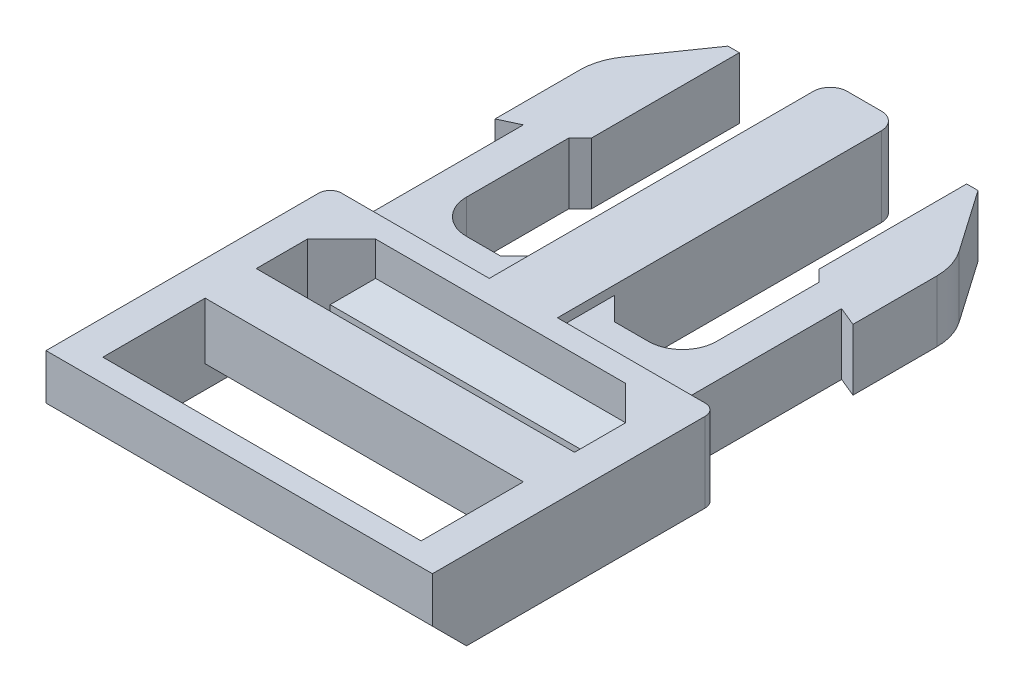
SolidWorks part; units mm, degrees
ref_plane "Front Plane" through (0, 0, 0) normal (0, 0, 1) x (1, 0, 0)
ref_plane "Top Plane" through (0, 0, 0) normal (0, 1, 0) x (1, 0, 0)
ref_plane "Right Plane" through (0, 0, 0) normal (1, 0, 0) x (0, 0, -1)
sketch "Sketch1" plane through (0, 0, 0) normal (0, 1, 0) x (1, 0, 0)
  line L1 (-14, 1.5) -> (14, 1.5)
  line L2 (-14, 1.5) -> (-14, -1.5)
  line L3 (-14, -1.5) -> (14, -1.5)
  line L4 (14, 1.5) -> (14, -1.5)
  line L5 (-14, 1.5) -> (14, -1.5) construction
  line L6 (-14, -1.5) -> (14, 1.5) construction
  point P0 (0, 0)
  dimension "D1" = 3
  dimension "D2" = 28
extrude "Boss-Extrude1" add sketch "Sketch1" along normal blind 7
sketch "Sketch2" plane through (0, 0, -1.5) normal (0, 0, -1) x (-1, 0, 0)
  line L0 (-14, 7) -> (14, 7) construction
  line L1 (14, 0) -> (11, 0)
  line L2 (14, 0) -> (14, 7)
  line L3 (14, 7) -> (11, 7)
  line L4 (11, 0) -> (11, 7)
  line L6 (-14, 0) -> (-11, 0)
  line L7 (-14, 0) -> (-14, 7)
  line L8 (-14, 7) -> (-11, 7)
  line L9 (-11, 0) -> (-11, 7)
  dimension "D1" = 3
  dimension "D2" = 3
extrude "Boss-Extrude2" add sketch "Sketch2" along normal blind 26
sketch "Sketch3" plane through (0, 0, -1.5) normal (0, 0, -1) x (-1, 0, 0)
  line L0 (-11, 7) -> (11, 7) construction
  line L1 (-3, 7) -> (3, 7)
  line L2 (-3, 7) -> (-3, 0)
  line L3 (-3, 0) -> (3, 0)
  line L4 (3, 7) -> (3, 0)
  line L5 (-11, 0) -> (11, 0) construction
  line L7 (-11, 0) -> (-11, 7) construction
  dimension "D1" = 6
  dimension "D2" = 8
extrude "Boss-Extrude3" add sketch "Sketch3" along normal blind 27
sketch "Sketch4" plane through (0, 7, 0) normal (0, 1, 0) x (1, 0, 0)
  line L0 (-14, 12.5) -> (-15.7, 11.7073)
  line L1 (-14, 27.5) -> (-14, -1.5) construction
  line L2 (-15.7, 11.7073) -> (-15.7, 16.7073)
  line L3 (-15.7, 16.7073) -> (-14, 19.5)
  line L4 (-14, 19.5) -> (-14, 12.5)
  line L5 (-3, 1.5) -> (-11, 1.5) construction
  line L6 (14, 12.5) -> (15.7, 11.8005)
  line L7 (14, -1.5) -> (14, 27.5) construction
  line L8 (15.7, 11.8005) -> (15.7, 16.8005)
  line L9 (15.7, 16.8005) -> (14, 19.5)
  line L10 (14, 19.5) -> (14, 12.5)
  dimension "D1" = 11
  dimension "D2" = 65
  dimension "D3" = 1.7
  dimension "D4" = 18
  dimension "D5" = 5
  dimension "D6" = 1.7
  dimension "D7" = 5
extrude "Boss-Extrude4" add sketch "Sketch4" against normal blind 7
chamfer "Chamfer1" distance 2 angle 45 2 edges at (3, 3.5, -1.5) (-3, 3.5, -1.5)
fillet "Fillet1" radius 3 2 edges at (11, 3.5, -1.5) (-11, 3.5, -1.5)
sketch "Sketch5" plane through (0, 7, 0) normal (0, 1, 0) x (1, 0, 0)
  line L0 (-14, 21.5) -> (-11, 27.5)
  line L1 (-14, 27.5) -> (-14, 19.5) construction
  line L2 (-11, 27.5) -> (-14, 27.5)
  line L3 (-14, 27.5) -> (-14, 21.5)
  line L4 (-5, 1.5) -> (-8, 1.5) construction
  line L5 (14, 21.5) -> (11, 27.5)
  line L6 (14, 19.5) -> (14, 27.5) construction
  line L7 (11, 27.5) -> (14, 27.5)
  line L9 (14, 27.5) -> (14, 21.5)
  dimension "D1" = 20
extrude "Cut-Extrude1" cut sketch "Sketch5" against normal blind 8
sketch "Sketch6" plane through (0, 0, 1.5) normal (0, 0, 1) x (1, 0, 0)
  line L0 (-14, 7) -> (-14, 0) construction
  line L1 (-17, 7) -> (17, 7)
  line L2 (-17, 7) -> (-17, 0)
  line L3 (-17, 0) -> (17, 0)
  line L4 (17, 7) -> (17, 0)
  line L5 (14, 7) -> (14, 0) construction
  line L6 (-14, 7) -> (14, 7) construction
  dimension "D1" = 3
  dimension "D2" = 3
  dimension "D3" = 0
extrude "Boss-Extrude5" add sketch "Sketch6" along normal blind 25
sketch "Sketch8" plane through (0, 7, 0) normal (0, 1, 0) x (1, 0, 0)
  line L0 (-17, -26.5) -> (-17, -1.5) construction
  line L1 (-14, -3.5) -> (14, -3.5)
  line L2 (-14, -3.5) -> (-14, -24.5)
  line L3 (-14, -24.5) -> (14, -24.5)
  line L4 (14, -3.5) -> (14, -24.5)
  line L5 (17, -26.5) -> (17, -1.5) construction
  line L6 (-14, -1.5) -> (-17, -1.5) construction
  line L7 (17, -26.5) -> (-17, -26.5) construction
  dimension "D1" = 3
  dimension "D2" = 3
  dimension "D3" = 2
  dimension "D4" = 2
extrude "Cut-Extrude2" cut sketch "Sketch8" against normal blind 25
chamfer "Chamfer2" distance 3 angle 45 2 edges at (14, 3.5, 3.5) (-14, 3.5, 3.5)
fillet "Fillet2" radius 1 2 edges at (17, 3.5, 1.5) (-17, 3.5, 1.5)
sketch "Sketch9" plane through (0, 7, 0) normal (0, 1, 0) x (1, 0, 0)
  line L0 (-14, -6.5) -> (-14, -24.5) construction
  line L1 (-14, -11.5) -> (14, -11.5)
  line L2 (-14, -11.5) -> (-14, -15.5)
  line L3 (-14, -15.5) -> (14, -15.5)
  line L4 (14, -11.5) -> (14, -15.5)
  line L5 (14, -24.5) -> (14, -6.5) construction
  line L6 (11, -3.5) -> (-11, -3.5) construction
  dimension "D1" = 8
extrude "Boss-Extrude6" add sketch "Sketch9" against normal blind 7
sketch "Sketch10" plane through (0, 0, 24.5) normal (0, 0, -1) x (-1, 0, 0)
  line L0 (14, 0) -> (14, 7) construction
  line L1 (-14, 0) -> (14, 0)
  line L2 (-14, 0) -> (-14, 2)
  line L3 (-14, 2) -> (14, 2)
  line L4 (14, 0) -> (14, 2)
  dimension "D1" = 2
extrude "Boss-Extrude7" add sketch "Sketch10" along normal blind 4
chamfer "Chamfer3" distance 1 angle 45 1 edges at (0, 2, 20.5)
chamfer "Chamfer4" distance 3 angle 45 1 edges at (0, 2, 24.5)
chamfer "Chamfer5" distance 2 angle 45 1 edges at (0, 0, 15.5)
fillet "Fillet4" radius 1.5 2 edges at (3, 3.5, -28.5) (-3, 3.5, -28.5)
sketch "Sketch11" plane through (-11, 0, 0) normal (1, 0, 0) x (0, 0, -1)
  line L0 (27.5, 0) -> (4.5, 0) construction
  line L1 (27.5, 7) -> (13.5, 7)
  line L2 (27.5, 7) -> (27.5, 0)
  line L3 (27.5, 0) -> (13.5, 0)
  line L4 (13.5, 7) -> (13.5, 0)
  dimension "D1" = 14
extrude "Boss-Extrude8" add sketch "Sketch11" along normal blind 1
chamfer "Chamfer6" distance 1 angle 45 1 edges at (-10, 3.5, -13.5)
sketch "Sketch12" plane through (11, 0, 0) normal (-1, 0, 0) x (0, 0, 1)
  line L0 (-27.5, 7) -> (-4.5, 7) construction
  line L1 (-27.5, 0) -> (-13.5, 0)
  line L2 (-27.5, 0) -> (-27.5, 7)
  line L3 (-27.5, 7) -> (-13.5, 7)
  line L4 (-13.5, 0) -> (-13.5, 7)
  dimension "D1" = 14
extrude "Boss-Extrude9" add sketch "Sketch12" along normal blind 1
chamfer "Chamfer7" distance 1 angle 45 1 edges at (10, 3.5, -13.5)
sketch "Sketch13" plane through (15.7, 0, 0) normal (1, 0, 0) x (0, 0, -1)
  line L0 (-1.5, 7) -> (-1.5, 0) construction
  line L1 (-1.5, 6.2) -> (28.5, 6.2)
  line L2 (28.5, 0.8) -> (28.5, 0)
  line L3 (-1.5, 0.8) -> (28.5, 0.8)
  line L5 (28.5, 7) -> (28.5, 0) construction
  line L6 (-1.5, 0.8) -> (-1.5, 0)
  line L7 (-1.5, 7) -> (28.5, 7)
  line L8 (-1.5, 7) -> (-1.5, 6.2)
  line L9 (-1.5, 0) -> (28.5, 0)
  line L10 (28.5, 7) -> (28.5, 6.2)
  dimension "D1" = 0.8
  dimension "D2" = 0.8
extrude "Cut-Extrude3" cut sketch "Sketch13" against normal blind 12.7
sketch "Sketch14" plane through (-15.7, 0, 0) normal (-1, 0, 0) x (0, 0, 1)
  line L0 (-28.5, 0) -> (-28.5, 7) construction
  line L1 (-28.5, 6.2) -> (1.5, 6.2)
  line L2 (1.5, 0.8) -> (1.5, 0)
  line L3 (-28.5, 0.8) -> (1.5, 0.8)
  line L5 (1.5, 7) -> (1.5, 0) construction
  line L6 (-28.5, 0.8) -> (-28.5, 0)
  line L7 (1.5, 7) -> (-28.5, 7)
  line L8 (1.5, 7) -> (1.5, 6.2)
  line L9 (1.5, 0) -> (-28.5, 0)
  line L10 (-28.5, 7) -> (-28.5, 6.2)
  dimension "D1" = 0.8
  dimension "D2" = 0.8
extrude "Cut-Extrude4" cut sketch "Sketch14" against normal blind 12.7
sketch "Sketch15" plane through (0, 6.2, 0) normal (0, 1, 0) x (1, 0, 0)
  line L0 (-15.7, 16.7073) -> (-15.7, 20.7469)
  line L1 (-15.7, 20.7469) -> (-11, 27.5)
  line L2 (-11, 27.5) -> (-14, 19.5)
  line L3 (-14, 19.5) -> (-15.7, 16.7073)
  line L4 (15.7, 16.8005) -> (15.7, 20.7469)
  line L5 (15.7, 20.7469) -> (11, 27.5)
  line L6 (11, 27.5) -> (14, 19.5)
  line L7 (14, 19.5) -> (15.7, 16.8005)
extrude "Boss-Extrude10" add sketch "Sketch15" against normal blind 5.4
fillet "Fillet5" radius 5 2 edges at (-15.7, 3.5, -20.7469) (15.7, 3.5, -20.7469)
chamfer "Chamfer8" distance 3 angle 45 1 edges at (0, 0, 26.5)
sketch "Sketch16" plane through (0, 0, 11.5) normal (0, 0, -1) x (-1, 0, 0)
  line L0 (14, 0) -> (14, 7) construction
  line L1 (-14, 7) -> (14, 7)
  line L2 (-14, 7) -> (-14, 5)
  line L3 (-14, 5) -> (14, 5)
  line L4 (14, 7) -> (14, 5)
  dimension "D1" = 2
extrude "Boss-Extrude11" add sketch "Sketch16" along normal blind 2
chamfer "Chamfer9" distance 2 angle 45 1 edges at (0, 5, 11.5)
sketch "Sketch17" plane through (0, 0, 3.5) normal (0, 0, 1) x (1, 0, 0)
  line L1 (15.6108, 0) -> (-15.0757, 0)
  line L2 (15.6108, 0) -> (15.6108, 2)
  line L3 (15.6108, 2) -> (-15.0757, 2)
  line L4 (-15.0757, 0) -> (-15.0757, 2)
  dimension "D1" = 2
extrude "Boss-Extrude12" add sketch "Sketch17" along normal blind 2
chamfer "Chamfer10" distance 2 angle 45 1 edges at (0, 2, 3.5)
chamfer "Chamfer11" distance 1.5 angle 45 1 edges at (0, 7, 9.5)
chamfer "Chamfer12" distance 1 angle 45 2 edges at (14, 0.5, 20.5) (-14, 0.5, 20.5)
